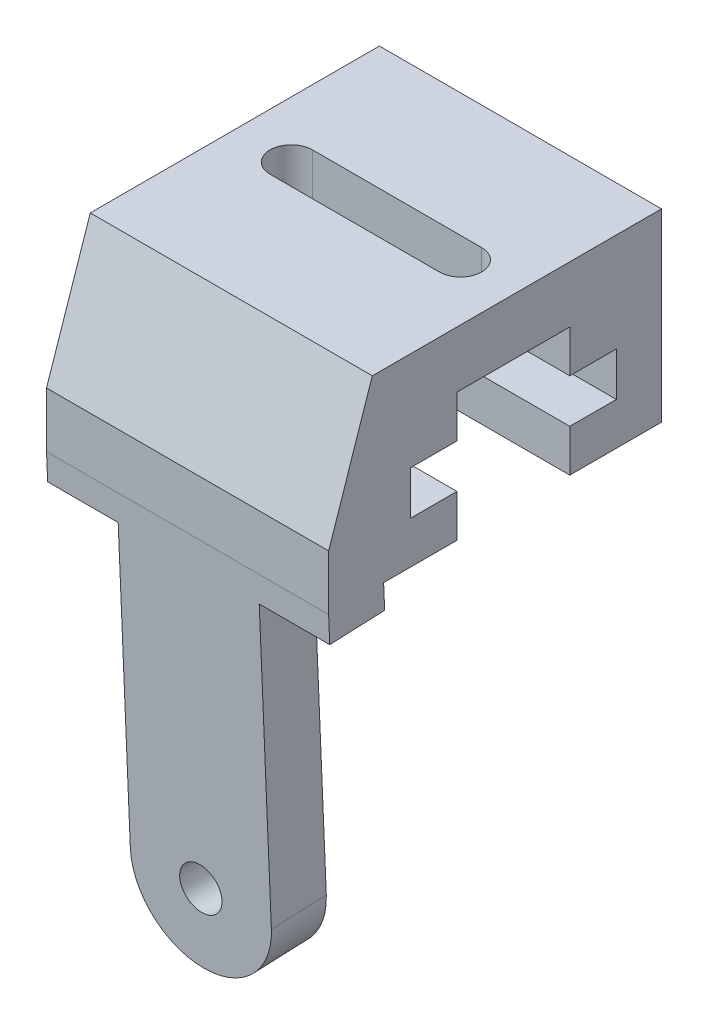
SolidWorks part; units mm, degrees
ref_plane "Alzado" through (0, 0, 0) normal (0, 0, 1) x (1, 0, 0)
ref_plane "Planta" through (0, 0, 0) normal (0, 1, 0) x (1, 0, 0)
ref_plane "Vista lateral" through (0, 0, 0) normal (1, 0, 0) x (0, 0, -1)
sketch "Croquis1" plane through (0, 0, 0) normal (1, 0, 0) x (0, 0, -1)
  line L0 (0, 0) -> (20.5, 0)
  line L1 (20.5, 0) -> (20.5, -13.1)
  line L2 (20.5, -13.1) -> (14, -13.1)
  line L3 (14, -13.1) -> (14, -10.1)
  line L4 (14, -10.1) -> (17.3, -10.1)
  line L5 (17.3, -10.1) -> (17.3, -7)
  line L6 (17.3, -7) -> (14, -7)
  line L7 (14, -7) -> (14, -4)
  line L8 (14, -4) -> (6, -4)
  line L9 (6, -4) -> (6, -7)
  line L10 (6, -7) -> (2.7, -7)
  line L11 (2.7, -7) -> (2.7, -10.1)
  line L12 (2.7, -10.1) -> (6, -10.1)
  line L13 (6, -10.1) -> (6, -13.1)
  line L14 (6, -13.1) -> (0.8, -13.1)
  line L15 (0.8, -13.1) -> (1.9465, -40.2355)
  line L16 (1.9465, -40.2355) -> (-1.9465, -40.4)
  line L17 (-1.9465, -40.4) -> (-3.1, -13.1)
  line L18 (-3.1, -13.1) -> (0.8, -13.1) construction
  line L19 (-3.1, -13.1) -> (-3.1, -9.2)
  line L20 (-3.1, -9.2) -> (0, 0)
  line L21 (17.3, -10.1) -> (10, -4) construction
  line L22 (10, -4) -> (2.7, -10.1) construction
  line L23 (0, -40.3178) -> (0, 0) construction
  line L24 (0.8733, -14.8355) -> (-3.0197, -15)
  dimension "D1" = 20.5
  dimension "D2" = 3.1
  dimension "D3" = 6.5
  dimension "D4" = 5.2
  dimension "D5" = 3
  dimension "D6" = 8
  dimension "D7" = 14.6
  dimension "D8" = 4
  dimension "D9" = 23.6
  dimension "D10" = 27.3
  dimension "D11" = 9.2
  dimension "D12" = 1.9
extrude "Saliente-Extruir1" add sketch "Croquis1" along normal mid plane 20 contours L24 L15 L14 L13 L12 L11 L10 L9 L8 L7 L6 L5 L4 L3 L2 L1 L0 L20 L19 L17 region at (0, -0.2796, -10.25)
extrude "Saliente-Extruir2" add sketch "Croquis1<4>" along normal mid plane 10 contours L15 L24 L17 L16 region at (0, -27.6178, 0.5366)
sketch "Croquis1<4>" plane through (0, 0, 0) normal (1, 0, 0) x (0, 0, -1) same geometry as "Croquis1"
fillet "Redondeo1" radius 5 2 edges at (-5, -40.3178, 0) (5, -40.3178, 0)
sketch "Croquis3" plane through (0, 0, 0) normal (0, 1, 0) x (1, 0, 0)
  line L0 (-6, 10.25) -> (6, 10.25) construction
  line L1 (-6, 11.75) -> (6, 11.75)
  line L2 (-6, 8.75) -> (6, 8.75)
  line L3 (0, 0) -> (0, 20.5) construction
  line L4 (10, 20.5) -> (-10, 20.5) construction
  arc A0 (-6, 11.75) -> (-6, 8.75) centre (-6, 10.25) ccw
  arc A1 (6, 8.75) -> (6, 11.75) centre (6, 10.25) ccw
  point P2 (0, 10.25)
  dimension "D2" = 1.5
  dimension "D1" = 12
extrude "Cortar-Extruir2" cut sketch "Croquis3" against normal up to next
sketch "Croquis4" plane through (0, 0, 0) normal (0, 0, 1) x (1, 0, 0)
  circle A0 centre (0, -35.4045) radius 1.5
  dimension "D1" = 3
  dimension "D2" = 35.4045
extrude "Cortar-Extruir3" cut sketch "Croquis4" along normal mid plane 10
